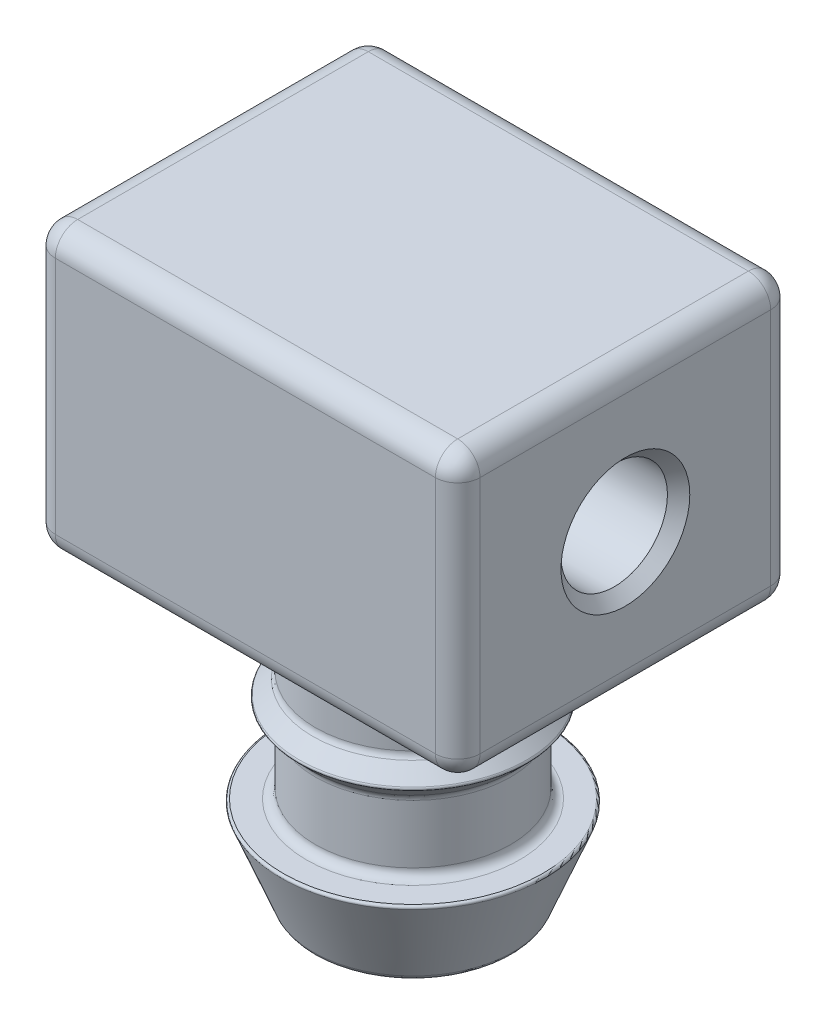
SolidWorks part; units mm, degrees
ref_plane "Front Plane" through (0, 0, 0) normal (0, 0, 1) x (1, 0, 0)
ref_plane "Top Plane" through (0, 0, 0) normal (0, 1, 0) x (1, 0, 0)
ref_plane "Right Plane" through (0, 0, 0) normal (1, 0, 0) x (0, 0, -1)
sketch "Sketch1" plane through (0, 0, 0) normal (0, 0, 1) x (1, 0, 0)
  line L0 (0, 7.7377) -> (0, -7.7377) construction
  line L1 (0, -12.7) -> (4.3656, -12.7)
  line L3 (4.3656, 0) -> (5.3975, 0)
  line L4 (5.3975, 0) -> (5.3975, 3.9688)
  line L5 (5.3975, 12.7) -> (0, 12.7)
  line L8 (0, 12.7) -> (0, -12.7)
  line L9 (4.3656, -12.7) -> (5.9531, -8.7312)
  line L21 (5.3975, 8.7312) -> (5.3975, 12.7)
  line L22 (5.3975, 0) -> (5.3975, 12.7) construction
  line L24 (5.3975, 8.7312) -> (3.81, 8.7312)
  line L25 (5.3975, 6.35) -> (0, 6.35) construction
  line L26 (3.81, 8.7312) -> (3.81, 3.9688)
  line L27 (3.81, 3.9688) -> (5.3975, 3.9688)
  line L32 (5.9531, -8.7312) -> (4.3656, -8.7312)
  line L33 (4.3656, -8.7312) -> (4.3656, -5.5563)
  line L34 (4.3656, -3.9687) -> (5.1594, -4.7625)
  line L35 (5.1594, -4.7625) -> (4.3656, -5.5563)
  line L36 (5.1594, -4.7625) -> (4.3656, -4.7625) construction
  line L37 (4.3656, -3.9687) -> (4.3656, 0)
  dimension "D7" = 1.5875
  dimension "D4" = 4.7625
  dimension "D1" = 12.7
  dimension "D2" = 3.9688
  dimension "D3" = 12.7
  dimension "D5" = 1.5875
  dimension "D6" = 10.795
  dimension "D8" = 8.7312
  dimension "D10" = 7.9375
  dimension "D11" = 45
  dimension "D9" = 0.7937
revolve "Revolve1" add sketch "Sketch1" angle 360 about L0 region at (2.4087, 0.0044, 0)
sketch "Sketch4" plane through (0, 12.7, 0) normal (0, 1, 0) x (1, 0, 0)
  line L1 (-9.5, -7.5) -> (9.5, -7.5)
  line L2 (-9.5, -7.5) -> (-9.5, 7.5)
  line L3 (-9.5, 7.5) -> (9.5, 7.5)
  line L4 (9.5, -7.5) -> (9.5, 7.5)
  line L5 (-9.5, -7.5) -> (9.5, 7.5) construction
  line L6 (-9.5, 7.5) -> (9.5, -7.5) construction
  point P0 (0, 0)
  dimension "D1" = 15
  dimension "D2" = 19
extrude "Boss-Extrude1" add sketch "Sketch4" against normal blind 12.7
sketch "Sketch2" plane through (0, 0, 0) normal (1, 0, 0) x (0, 0, -1)
  line L0 (0, 0) -> (0, 6.35) construction
  line L1 (-7.5, 12.7) -> (7.5, 12.7) construction
  line L2 (0, 6.35) -> (0, 12.7) construction
  line L4 (-7.5, 12.7) -> (7.5, 12.7) construction
  circle A0 centre (0, 6.35) radius 2.3813
  point P2 (0, 5.8626)
  point P7 (0, 12.7)
  dimension "D1" = 4.7625
extrude "Cut-Extrude1" cut sketch "Sketch2" against normal through all both and the other way through all contours A0
sketch "Sketch3" plane through (0, 12.7, 0) normal (0, 1, 0) x (1, 0, 0)
  circle A0 centre (0, 0) radius 2.3813
  dimension "D1" = 4.7625
fillet "Fillet3" radius 0.3969 5 edges at (0, -12.7, 4.3656) (0, -8.7312, 4.3656) (0, 0, 4.3656) (0, -3.9687, 4.3656) (0, -5.5563, 4.3656)
fillet "Fillet4" radius 0.0992 2 edges at (0, -8.7313, 5.9531) (0, -4.7625, 5.1594)
chamfer "Chamfer1" distance 0.5 angle 45 2 edges at (9.5, 6.35, -2.3813) (-9.5, 6.35, -2.3813)
fillet "Fillet5" radius 1 12 edges at (0, 12.7, 7.5) (-9.5, 12.7, 0) (9.5, 12.7, 0) (-9.5, 6.35, -7.5) (0, 0, -7.5) (9.5, 6.35, -7.5) (0, 12.7, -7.5) (9.5, 0, 0) (-9.5, 0, 0) (-9.5, 6.35, 7.5) (0, 0, 7.5) (9.5, 6.35, 7.5)
